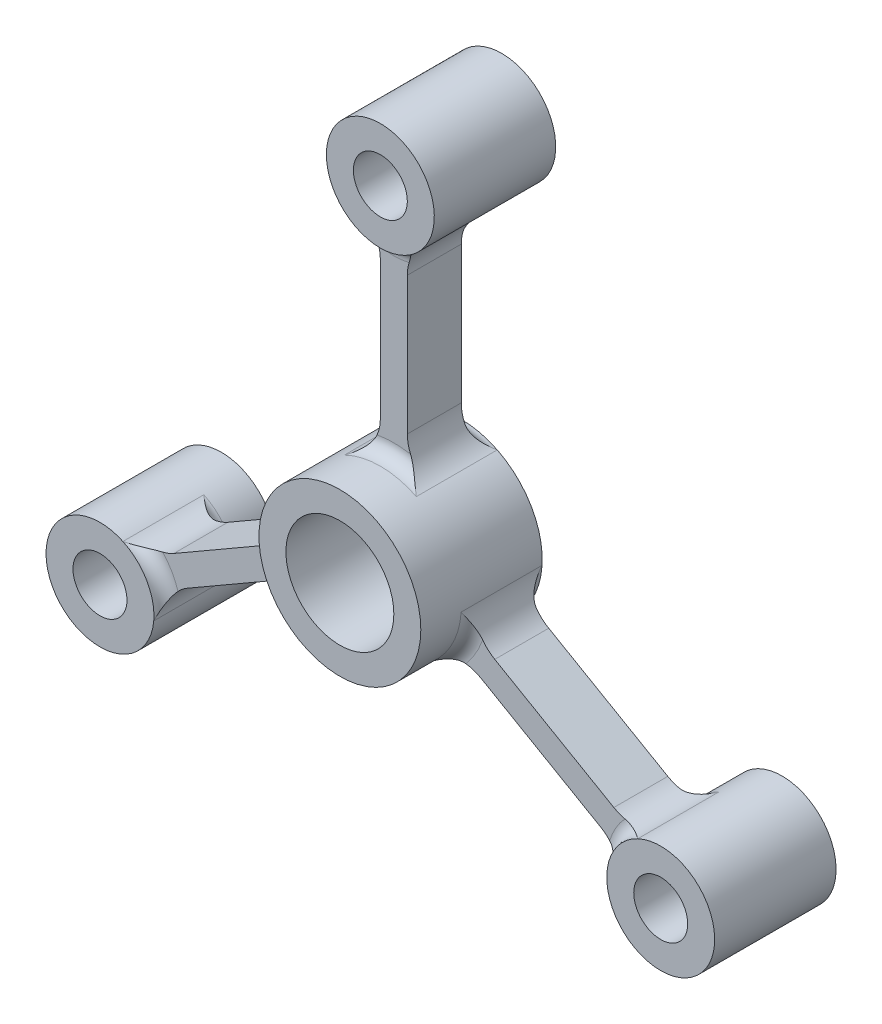
SolidWorks part; units mm, degrees
material "Alloy Steel"
ref_plane "Plane1" through (0, 0, 0) normal (0, 0, 1) x (1, 0, 0)
ref_plane "Plane2" through (0, 0, 0) normal (0, 1, 0) x (1, 0, 0)
ref_plane "Plane3" through (0, 0, 0) normal (1, 0, 0) x (0, 0, -1)
sketch "Sketch2" plane through (0, 0, 0) normal (0, 0, 1) x (1, 0, 0)
  line L0 (0, 76.2) -> (0, 0) construction
  line L1 (0, 0) -> (65.9911, -38.1) construction
  line L2 (-65.9911, -38.1) -> (0, 0) construction
  line L3 (-3.175, 63.9033) -> (-3.175, 18.7836)
  line L4 (3.175, 63.9033) -> (3.175, 18.7836)
  line L5 (17.8545, -6.6421) -> (56.9294, -29.202)
  line L6 (14.6795, -12.1414) -> (53.7544, -34.7013)
  line L7 (-56.9294, -29.202) -> (-17.8545, -6.6421)
  line L8 (-53.7544, -34.7013) -> (-14.6795, -12.1414)
  arc A0 (17.8545, -6.6421) -> (3.175, 18.7836) centre (0, 0) ccw
  arc A1 (3.175, 63.9033) -> (-3.175, 63.9033) centre (0, 76.2) ccw
  arc A2 (53.7544, -34.7013) -> (56.9294, -29.202) centre (65.9911, -38.1) ccw
  arc A3 (-56.9294, -29.202) -> (-53.7544, -34.7013) centre (-65.9911, -38.1) ccw
  arc A4 (-14.6795, -12.1414) -> (14.6795, -12.1414) centre (0, 0) ccw
  arc A5 (-3.175, 18.7836) -> (-17.8545, -6.6421) centre (0, 0) ccw
  dimension "D1" = 38.1
  dimension "D2" = 25.4
  dimension "D3" = 120
  dimension "D4" = 120
  dimension "D5" = 76.2
  dimension "D6" = 3.175
extrude "Base-Extrude" add sketch "Sketch2" along normal blind 12.7
sketch "Sketch3" plane through (0, 0, 12.7) normal (0, 0, 1) x (1, 0, 0)
  circle A0 centre (0, 0) radius 19.05
extrude "Boss-Extrude1" add sketch "Sketch3" along normal blind 12.7
sketch "Sketch5" plane through (0, 0, 0) normal (0, 0, -1) x (-1, 0, 0)
  circle A0 centre (65.9911, -38.1) radius 12.7
  circle A1 centre (-65.9911, -38.1) radius 12.7
  circle A2 centre (0, 76.2) radius 12.7
extrude "Boss-Extrude2" add sketch "Sketch5" along normal blind 12.7
sketch "Sketch10" plane through (0, 0, 12.7) normal (0, 0, 1) x (1, 0, 0)
  circle A0 centre (-65.9911, -38.1) radius 12.7
extrude "Boss-Extrude3" add sketch "Sketch10" along normal blind 3.175
sketch "Sketch11" plane through (0, 0, 12.7) normal (0, 0, 1) x (1, 0, 0)
  circle A0 centre (65.9911, -38.1) radius 12.7
extrude "Boss-Extrude4" add sketch "Sketch11" along normal blind 3.175
sketch "Sketch12" plane through (0, 0, 12.7) normal (0, 0, 1) x (1, 0, 0)
  circle A0 centre (0, 76.2) radius 12.7
  dimension "D1" = 25.4
extrude "Boss-Extrude5" add sketch "Sketch12" along normal blind 3.175
sketch "Sketch7" plane through (0, 0, 0) normal (0, 0, -1) x (-1, 0, 0)
  circle A0 centre (0, 76.2) radius 6.35
  circle A1 centre (65.9911, -38.1) radius 6.35
  circle A2 centre (-65.9911, -38.1) radius 6.35
  dimension "D1" = 12.7
extrude "Cut-Extrude2" cut sketch "Sketch7" against normal through all and the other way blind 12.7
sketch "Sketch13" plane through (0, 0, 0) normal (0, 0, -1) x (-1, 0, 0)
  circle A0 centre (0, 0) radius 19.05
extrude "Boss-Extrude6" add sketch "Sketch13" along normal blind 3.175
sketch "Sketch4" plane through (0, 0, 25.4) normal (0, 0, 1) x (1, 0, 0)
  circle A0 centre (0, 0) radius 12.7
  dimension "D1" = 25.4
extrude "Cut-Extrude1" cut sketch "Sketch4" against normal through all
fillet "Fillet6" radius 9.525 6 edges
fillet "Fillet8" radius 3.175 6 edges at (-16.4978, -9.525, 0) (0, 19.05, 0) (16.4978, -9.525, 0)
fillet "Fillet9" radius 9.525 6 edges at (-3.175, 63.9033, 6.35) (3.175, 63.9033, 6.35) (56.9294, -29.202, 6.35) (53.7544, -34.7013, 6.35)
fillet "Fillet10" radius 3.175 6 edges at (-54.9926, -31.75, 12.7) (0, 63.5, 12.7) (0, 63.5, 0) (54.9926, -31.75, 0) (54.9926, -31.75, 12.7)
